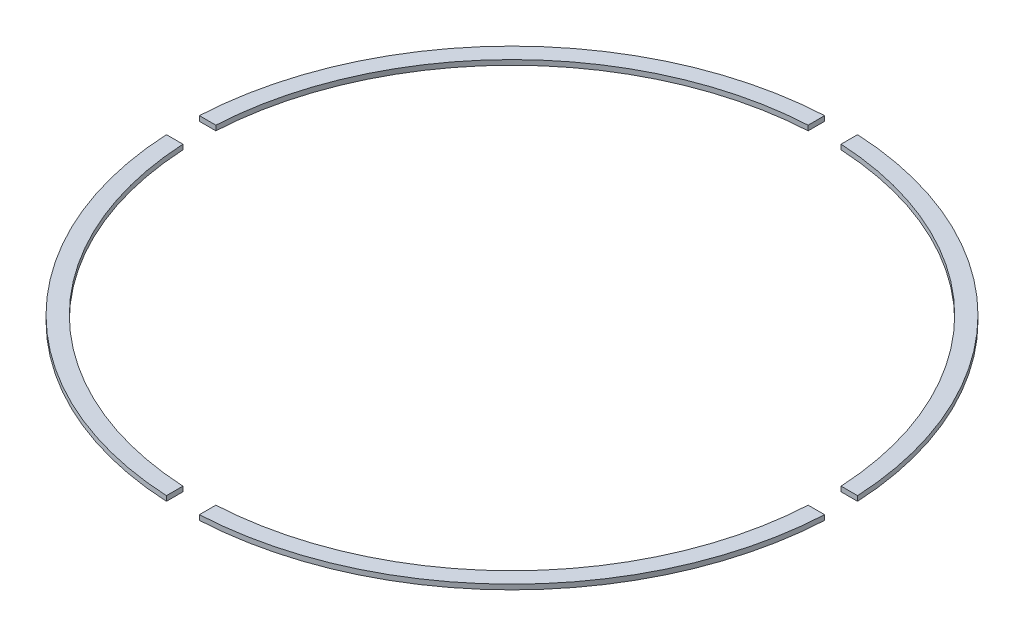
SolidWorks part; units mm, degrees
ref_plane "Front Plane" through (0, 0, 0) normal (0, 0, 1) x (1, 0, 0)
ref_plane "Top Plane" through (0, 0, 0) normal (0, 1, 0) x (1, 0, 0)
ref_plane "Right Plane" through (0, 0, 0) normal (1, 0, 0) x (0, 0, -1)
sketch "Sketch1" plane through (0, 0, 0) normal (0, 1, 0) x (1, 0, 0)
  line L0 (-200, 0) -> (200, 0) construction
  circle A0 centre (0, 0) radius 200
  circle A1 centre (0, 0) radius 190
  dimension "D1" = 400
  dimension "D2" = 380
extrude "Boss-Extrude1" add sketch "Sketch1" along normal mid plane 3
sketch "Sketch3" plane through (0, 0, 0) normal (0, 0, 1) x (1, 0, 0)
  line L0 (0, -250) -> (0, 250) construction
  dimension "D1" = 500
sketch "roll" plane through (0, 0, 0) normal (0, 1, 0) x (1, 0, 0)
  line L0 (0, -195) -> (0, 195) construction
  dimension "D1" = 390
sketch "circle" plane through (0, 0, 0) normal (0, 1, 0) x (1, 0, 0)
  circle A0 centre (0, 0) radius 195 construction
  circle A1 centre (0, 0) radius 190 construction
  dimension "D1" = 5
sketch "pitch" plane through (0, 0, 0) normal (0, 1, 0) x (1, 0, 0)
  line L0 (-195, 0) -> (195, 0) construction
  circle A1 centre (0, 0) radius 195 construction
sketch "Sketch4" plane through (0, 0, 0) normal (0, 1, 0) x (1, 0, 0)
  line L1 (-10, 200) -> (10, 200)
  line L2 (-10, 200) -> (-10, -200)
  line L3 (-10, -200) -> (10, -200)
  line L4 (10, 200) -> (10, -200)
  line L5 (-10, 200) -> (10, -200) construction
  line L6 (-10, -200) -> (10, 200) construction
  line L7 (200, 10) -> (-200, 10)
  line L8 (200, 10) -> (200, -10)
  line L9 (200, -10) -> (-200, -10)
  line L10 (-200, 10) -> (-200, -10)
  line L11 (200, 10) -> (-200, -10) construction
  line L12 (200, -10) -> (-200, 10) construction
  circle A0 centre (0, 0) radius 200 construction
  point P0 (0, 0)
  point P8 (0, 0)
  dimension "D1" = 20
extrude "quadruple" cut sketch "Sketch4" against normal through all both and the other way through all contours L9 L10 L7 L8 | L4 L3 L2 L1
ref_axis "Axis1" through (0, -148.0362, 0) along (0, 1, 0)
